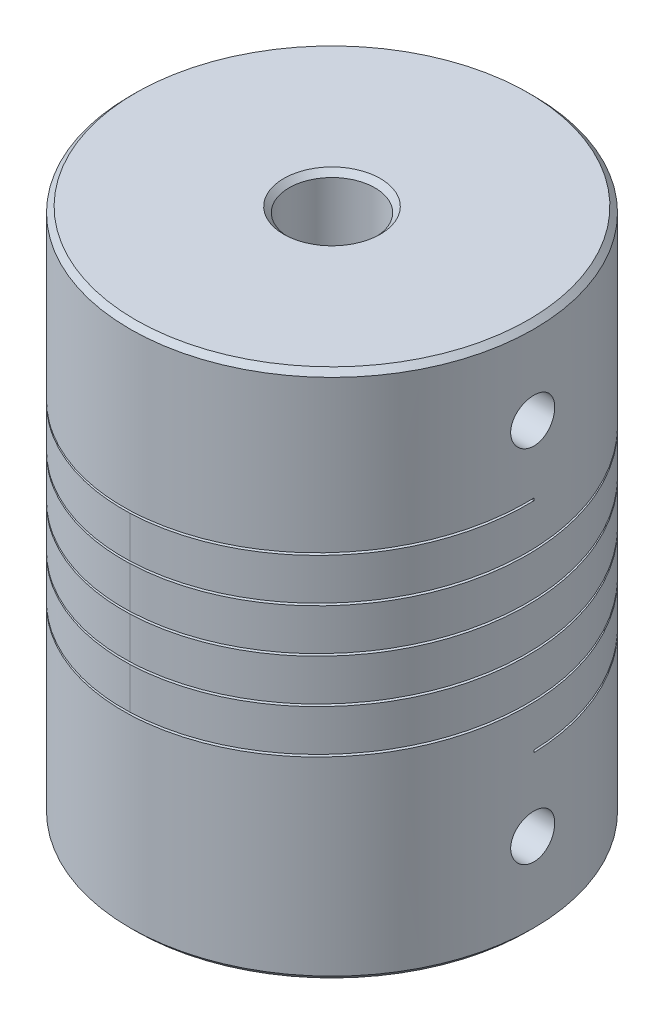
SolidWorks part; units mm, degrees
ref_plane "Front Plane" through (0, 0, 0) normal (0, 0, 1) x (1, 0, 0)
ref_plane "Top Plane" through (0, 0, 0) normal (0, 1, 0) x (1, 0, 0)
ref_plane "Right Plane" through (0, 0, 0) normal (1, 0, 0) x (0, 0, -1)
sketch "Sketch1" plane through (0, 0, 0) normal (0, 1, 0) x (1, 0, 0)
  circle A0 centre (0, 0) radius 9.398
  circle A1 centre (0, 0) radius 2
  dimension "D1" = 4
  dimension "D2" = 18.796
extrude "Boss-Extrude1" add sketch "Sketch1" along normal mid plane 24.638
sketch "Sketch6" plane through (0, 12.319, 0) normal (0, 1, 0) x (1, 0, 0)
  circle A0 centre (0, 0) radius 2
  dimension "D1" = 4
extrude "Cut-Extrude2" [suppressed] cut sketch "Sketch6" against normal blind 12.319
chamfer "Chamfer1" distance 0.25 angle 45 4 edges at (0, -12.319, 2) (0, -12.319, 9.398) (0, 12.319, 2) (0, 12.319, 9.398)
hole_wizard "M2.5x0.45 Tapped Hole1" positions "3DSketch1" profile "Sketch2" tap size "M2.5x0.45" standard "ANSI Metric" end condition up to next
sketch3d "3DSketch1"
  line L0 (0, -8.382, -9.398) -> (0, -8.382, 0) construction
  line L3 (0, 12.319, 0) -> (0, -12.319, 0) construction
  line L6 (9.398, -8.382, 0) -> (0, -8.382, 0) construction
  line L8 (9.398, 8.382, 0) -> (0, 8.382, 0) construction
  line L11 (0, 8.382, -9.398) -> (0, 8.382, 0) construction
  circle A2 centre (0, -12.319, 0) radius 2.25 construction
  point P0 (9.398, 8.382, 0)
  point P2 (9.398, -8.382, 0)
  point P4 (0, 8.382, -9.398)
  point P6 (0, -8.382, -9.398)
  point P28 (0, -10.069, 0)
  dimension "D1" = 3.937
  dimension "D2" = 3.937
sketch "Sketch2" plane through (9.398, 8.382, 0) normal (0, 1, 0) x (0, 0, -1)
  line L0 (0, 0) -> (0, 7.398)
  line L1 (0, 7.398) -> (1.025, 7.398)
  line L2 (1.025, 7.398) -> (1.025, 0)
  line L5 (1.025, 0) -> (0, 0)
  line L11 (0, -6.35) -> (0, 107.95) construction
  dimension "Thru Tap Drill Dia." = 2.05
  dimension "Thru Tap Drill Depth" = 7.398
cosmetic thread "Hole Thread1" parameters "D2"=2.5
cosmetic thread "Hole Thread2" parameters "D2"=2.5
cosmetic thread "Hole Thread3" parameters "D2"=2.5
cosmetic thread "Hole Thread4" parameters "D2"=2.5
ref_plane "Plane1" through (0, -4.953, 0) normal (0, -1, 0) x (-1, 0, 0)
sketch "Sketch3" plane through (0, -4.953, 0) normal (0, -1, 0) x (-1, 0, 0)
  circle A0 centre (0, 0) radius 9.398 construction
  circle A1 centre (0, 0) radius 9.398
curve "Helix/Spiral1" pitch 2.032 height 10.16 radius 9.398 centre (0, -4.953, 0) axis (0, 1, 0) start towards (1, 0, 0)
sketch "Sketch4" plane through (0, 0, 0) normal (0, 0, 1) x (1, 0, 0)
  line L0 (9.398, -5.0055) -> (2, -5.0055)
  line L1 (9.398, -7.357) -> (9.398, 7.357) construction
  line L2 (9.398, -4.953) -> (2, -4.953) construction
  line L3 (-10.0628, -4.953) -> (10.0628, -4.953) construction
  line L5 (9.398, -5.0055) -> (9.398, -4.9005)
  line L6 (9.398, -4.9005) -> (2, -4.9005)
  line L7 (2, -4.9005) -> (2, -5.0055)
  line L8 (2, -5.0055) -> (2, -12.069) construction
  line L11 (-2, -12.069) -> (2, -12.069) construction
  line L12 (-2, -12.069) -> (2, -12.069) construction
  dimension "D1" = 0.105
sweep "Cut-Sweep3" cut profiles "Sketch4" path "Helix/Spiral1" align with end faces yes
equation "\"D1@Cut-Extrude2\" = \"D1@Boss-Extrude1\" / 2"
